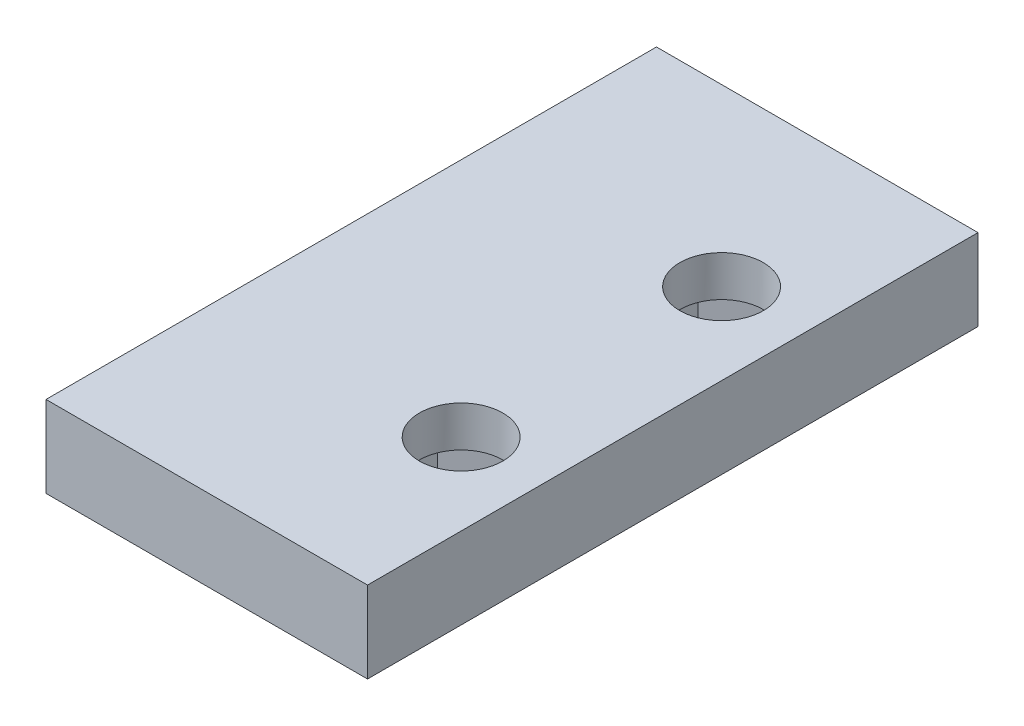
SolidWorks part; units mm, degrees
ref_plane "前视基准面" through (0, 0, 0) normal (0, 0, 1) x (1, 0, 0)
ref_plane "上视基准面" through (0, 0, 0) normal (0, 1, 0) x (1, 0, 0)
ref_plane "右视基准面" through (0, 0, 0) normal (1, 0, 0) x (0, 0, -1)
other "Configuration Table"
sketch "草图1" plane through (0, 0, 0) normal (0, 1, 0) x (1, 0, 0)
  line L1 (0, 0) -> (15.8, 0)
  line L2 (0, 0) -> (0, 30)
  line L3 (0, 30) -> (15.8, 30)
  line L4 (15.8, 0) -> (15.8, 30)
  dimension "D1" = 15.8
  dimension "D2" = 30
extrude "凸台-拉伸1" add sketch "草图1" along normal blind 4
sketch "草图2" plane through (0, 4, 0) normal (0, 1, 0) x (1, 0, 0)
  line L0 (11.8, 30) -> (11.8, 0) construction
  line L3 (0, 15) -> (15.8, 15) construction
  line L16 (0, 30) -> (0, 0) construction
  line L17 (15.8, 0) -> (15.8, 30) construction
  circle A0 centre (11.8, 21.4) radius 2.05
  circle A1 centre (11.8, 8.6) radius 2.05
  dimension "D1" = 4.1
  dimension "D2" = 4.1
  dimension "D3" = 12.8
  dimension "D4" = 4
extrude "切除-拉伸1" cut sketch "草图2" against normal through all
sketch "草图5" plane through (0, 0, 0) normal (0, -1, 0) x (1, 0, 0)
  line L1 (14.55, -7.0123) -> (11.8, -5.4246)
  line L2 (11.8, -5.4246) -> (9.05, -7.0123)
  line L3 (9.05, -7.0123) -> (9.05, -10.1877)
  line L4 (9.05, -10.1877) -> (11.8, -11.7754)
  line L5 (11.8, -11.7754) -> (14.55, -10.1877)
  line L6 (14.55, -10.1877) -> (14.55, -7.0123)
  line L7 (9.05, -22.9877) -> (11.8, -24.5754)
  line L8 (11.8, -24.5754) -> (14.55, -22.9877)
  line L9 (14.55, -22.9877) -> (14.55, -19.8123)
  line L10 (14.55, -19.8123) -> (11.8, -18.2246)
  line L11 (11.8, -18.2246) -> (9.05, -19.8123)
  line L12 (9.05, -19.8123) -> (9.05, -22.9877)
  circle A0 centre (11.8, -8.6) radius 2.75 construction
  circle A1 centre (11.8, -21.4) radius 2.75 construction
  dimension "D1" = 5.5
  dimension "D2" = 5.5
extrude "切除-拉伸2" cut sketch "草图5" against normal blind 2
ref_axis "基准轴1" through (11.8, 2, -21.4) along (0, 1, 0)
ref_axis "基准轴2" through (11.8, 2, -8.6) along (0, 1, 0)
